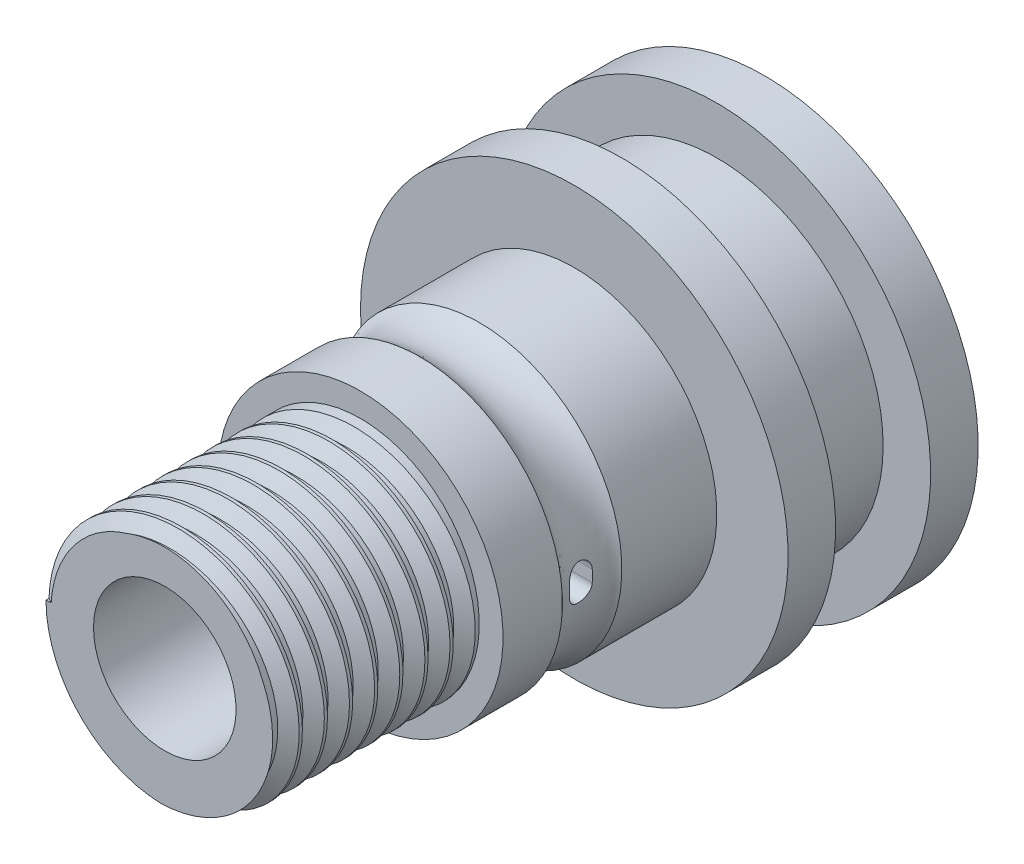
SolidWorks part; units mm, degrees
ref_plane "前视基准面" through (0, 0, 0) normal (0, 0, 1) x (1, 0, 0)
ref_plane "上视基准面" through (0, 0, 0) normal (0, 1, 0) x (1, 0, 0)
ref_plane "右视基准面" through (0, 0, 0) normal (1, 0, 0) x (0, 0, -1)
sketch "草图1" plane through (0, 0, 0) normal (0, 1, 0) x (1, 0, 0)
  line L0 (0, 18.2368) -> (0, -18.2368) construction
  line L1 (19.7895, 0) -> (-19.7895, 0) construction
  line L2 (-5.2, 8) -> (-9, 8)
  line L3 (-9, 8) -> (-9, 6)
  line L4 (-9, 6) -> (-7, 6)
  line L5 (-7, 6) -> (-7, 2)
  line L6 (-7, 2) -> (-9, 2)
  line L7 (-9, 2) -> (-9, 0)
  line L8 (-9, 0) -> (-6, 0)
  line L9 (-6, 0) -> (-6, -4)
  line L10 (-6, -6.5) -> (-6, -9)
  line L11 (-6, -9) -> (-5, -9)
  line L12 (-5, -9) -> (-5, -17.2368)
  line L13 (-5, -17.2368) -> (-3, -17.2368)
  line L14 (-3, -17.2368) -> (-3, 2)
  line L15 (-3, 2) -> (-5.2, 2)
  line L16 (-5.2, 2) -> (-5.2, 8)
  line L17 (-19.3158, -5.25) -> (-1.1579, -5.25) construction
  spline S0 degree 3 poles (-6, -4) (-5.4667, -4.476) (-5.4667, -6.024) (-6, -6.5) knots 0 0 0 0 1 1 1 1
  point P4 (0, 0)
  point P8 (0, 0)
  point P26 (-5.5, -9)
  point P30 (-10.2368, -5.25)
  dimension "D7" = 15
  dimension "D14" = 0.4
  dimension "D1" = 5
  dimension "D2" = 4
  dimension "D3" = 2
  dimension "D4" = 2
  dimension "D5" = 1.8
  dimension "D6" = 6
  dimension "D8" = 2.5
  dimension "D9" = 2
  dimension "D10" = 7
  dimension "D11" = 2
  dimension "D12" = 9
  dimension "D13" = 4
  dimension "D15" = 2.5
  dimension "D16" = 5.2
revolve "旋转1" add sketch "草图1" angle 360 about L0
thread "螺纹线1" pitch 1.0583 method cut profile "螺纹线轮廓1" start angle 0, offset 0.8, length 8.1, pitch 1.0583, diameter 10
ref_plane "基准面1" through (-5, 0, 18.0368) normal (0, -1, 0) x (-1, 0, 0)
sketch "螺纹线轮廓1" plane through (-5, 0, 18.0368) normal (0, -1, 0) x (-1, 0, 0)
  line L0 (0, 0) -> (0, 1.0583) construction
  line L11 (0, 0) -> (0, 0.926)
  line L12 (0, 0.926) -> (-0.5728, 0.5953)
  line L13 (-0.5728, 0.5953) -> (-0.5728, 0.3307)
  line L15 (-0.5728, 0.3307) -> (0, 0)
  line L17 (-0.5728, 0.463) -> (0, 0.463) construction
  point P2 (0, 0)
  dimension "Pitch" = 1.0583
  dimension "Profile_Angle" = 60
  dimension "Profile_Land" = 0.2646
  dimension "Profile_Height" = 0.5728
thread "螺纹线2" pitch 1.0583 method extrude profile "螺纹线轮廓2" start angle 0, offset 0, length 5, pitch 1.0583, diameter 10.4
ref_plane "基准面2" through (5.2, 0, -8) normal (0, -1, 0) x (1, 0, 0)
sketch "螺纹线轮廓2" plane through (5.2, 0, -8) normal (0, -1, 0) x (1, 0, 0)
  line L0 (0, 0) -> (0, 1.0583) construction
  line L11 (0, 0) -> (0, 0.926)
  line L12 (0, 0.926) -> (-0.5728, 0.5953)
  line L13 (-0.5728, 0.5953) -> (-0.5728, 0.3307)
  line L15 (-0.5728, 0.3307) -> (0, 0)
  line L17 (-0.5728, 0.463) -> (0, 0.463) construction
  point P2 (0, 0)
  dimension "Pitch" = 1.0583
  dimension "Profile_Angle" = 60
  dimension "Profile_Land" = 0.2646
  dimension "Profile_Height" = 0.5728
sketch "草图6" plane through (0, 0, 0) normal (1, 0, 0) x (0, 0, -1)
  line L0 (-23.0613, 0) -> (23.0613, 0) construction
  line L1 (-5.365, 0.25) -> (-5.365, -0.25) construction
  line L6 (-5.365, 11.6843) -> (-5.365, -11.6843) construction
  line L7 (-4.865, 0.25) -> (-4.865, -0.25)
  line L8 (-5.865, 0.25) -> (-5.865, -0.25)
  arc A0 (-4.865, 0.25) -> (-5.865, 0.25) centre (-5.365, 0.25) ccw
  arc A1 (-5.865, -0.25) -> (-4.865, -0.25) centre (-5.365, -0.25) ccw
  point P4 (0, 0)
  point P7 (-5.365, 0)
  point P14 (-5.365, 0)
  dimension "D1" = 0.5
  dimension "D2" = 1
extrude "切除-拉伸1" cut sketch "草图6" against normal mid plane 20
